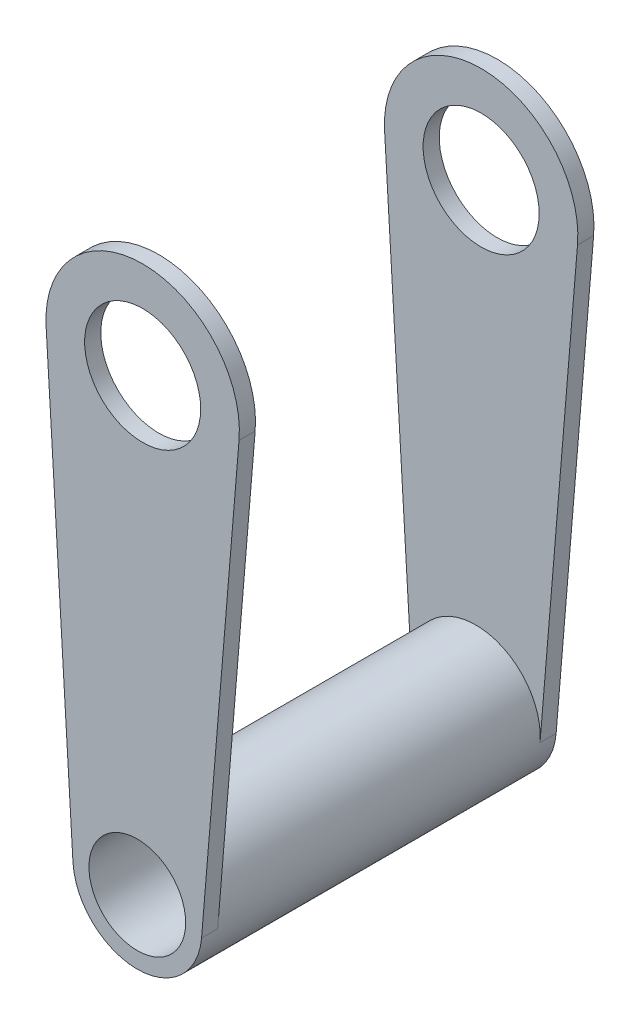
SolidWorks part; units mm, degrees
ref_plane "前基準面" through (0, 0, 0) normal (0, 0, 1) x (1, 0, 0)
ref_plane "上基準面" through (0, 0, 0) normal (0, 1, 0) x (1, 0, 0)
ref_plane "右基準面" through (0, 0, 0) normal (1, 0, 0) x (0, 0, -1)
sketch "草圖1" plane through (0, 0, 0) normal (0, 0, 1) x (1, 0, 0)
  line L0 (132.3027, 75.1984) -> (136.4634, 5.3222)
  line L1 (156.4112, 5.0861) -> (162.2244, 74.8443)
  arc A1 (162.2244, 74.8443) -> (132.3027, 75.1984) centre (147.2762, 76.09) ccw
  circle A2 centre (147.2762, 76.09) radius 9
  arc A4 (156.4112, 5.0861) -> (136.4634, 5.3222) centre (146.4457, 5.9166) cw
  circle A5 centre (146.4457, 5.9166) radius 7.5
  dimension "D1" = 10
  dimension "D2" = 15
  dimension "D4" = 18
  dimension "D5" = 15
  dimension "D3" = 70
extrude "填料-伸長1" add sketch "草圖1" against normal blind 2.5 from offset 25 offset against normal yes
sketch "草圖5" plane through (0, 0, 0) normal (0, 0, 1) x (1, 0, 0)
  circle A0 centre (146.4457, 5.9166) radius 10
  circle A1 centre (146.4457, 5.9166) radius 7.5
  dimension "D1" = 20
  dimension "D2" = 15
extrude "填料-伸長5" add sketch "草圖5" along normal mid plane 55
extrude "填料-伸長6" add sketch "草圖1<3>" along normal blind 2.5 from offset 25
sketch "草圖1<3>" plane through (0, 0, 0) normal (0, 0, 1) x (1, 0, 0) same geometry as "草圖1"
